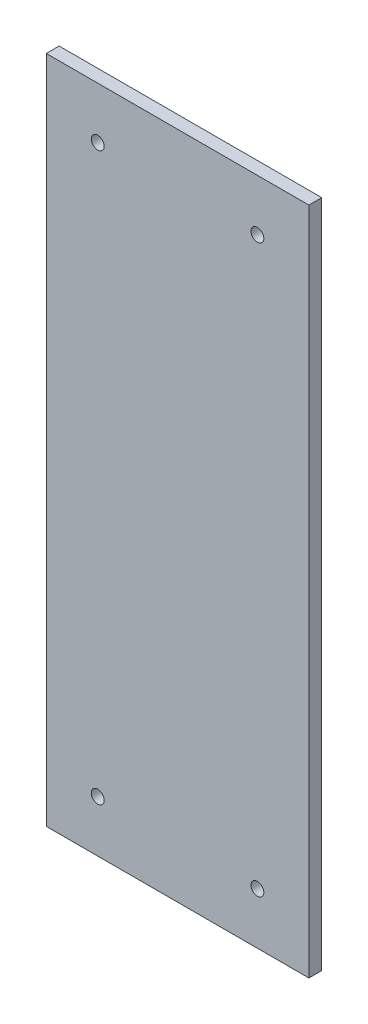
SolidWorks part; units mm, degrees
material "6061 Alloy"
ref_plane "Front" through (0, 0, 0) normal (0, 0, 1) x (1, 0, 0)
ref_plane "Top" through (0, 0, 0) normal (0, 1, 0) x (1, 0, 0)
ref_plane "Right" through (0, 0, 0) normal (1, 0, 0) x (0, 0, -1)
sketch "Sketch1" plane through (0, 0, 0) normal (0, 0, 1) x (1, 0, 0)
  line L1 (0, 0) -> (129.54, 0)
  line L2 (0, 0) -> (0, 330.2)
  line L3 (0, 330.2) -> (129.54, 330.2)
  line L4 (129.54, 0) -> (129.54, 330.2)
  dimension "D1" = 330.2
  dimension "D2" = 129.54
extrude "Boss-Extrude1" add sketch "Sketch1" along normal blind 6.35
sketch "Sketch2" plane through (0, 0, 6.35) normal (0, 0, 1) x (1, 0, 0)
  line L0 (0, 330.2) -> (0, 0) construction
  line L1 (129.54, 330.2) -> (0, 330.2) construction
  circle A0 centre (25.4, 304.8) radius 3.175
  dimension "D3" = 6.35
  dimension "D1" = 25.4
  dimension "D2" = 25.4
extrude "Cut-Extrude1" cut sketch "Sketch2" against normal blind 6.35
pattern_linear "LPattern1" count 2 spacing 78.74 along (1, 0, 0) count 2 spacing 279.4 along (0, -1, 0) of "Cut-Extrude1"
